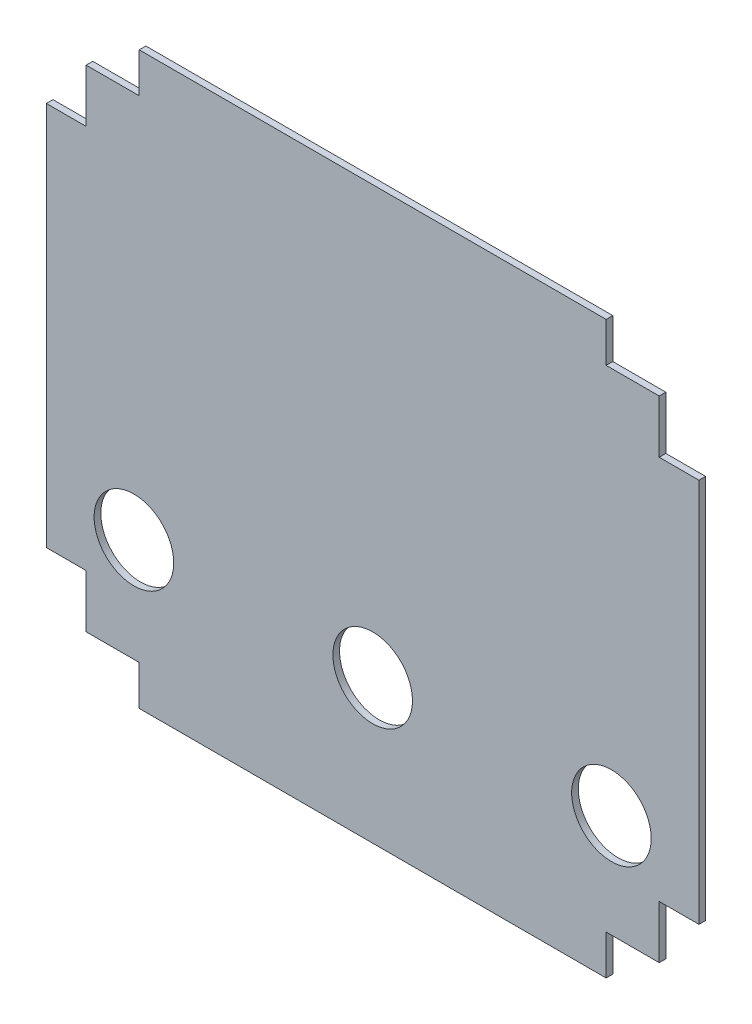
SolidWorks part; units mm, degrees
material "Acrílico (Impacto medio-alto)"
ref_plane "Alzado" through (0, 0, 0) normal (0, 0, 1) x (1, 0, 0)
ref_plane "Planta" through (0, 0, 0) normal (0, 1, 0) x (1, 0, 0)
ref_plane "Vista lateral" through (0, 0, 0) normal (1, 0, 0) x (0, 0, -1)
sketch "Croquis1" plane through (0, 0, 0) normal (0, 0, 1) x (1, 0, 0)
  line L0 (-246, 0) -> (246, 0)
  line L1 (0, 0) -> (0, 215) construction
  line L2 (-246, -145) -> (-246, 145)
  line L3 (-246, 145) -> (-216, 145)
  line L4 (-216, 145) -> (-216, 185)
  line L5 (-216, 185) -> (-176, 185)
  line L6 (-176, 185) -> (-176, 215)
  line L7 (-176, 215) -> (176, 215)
  line L8 (246, -145) -> (246, 145)
  line L9 (246, 145) -> (216, 145)
  line L10 (216, 145) -> (216, 185)
  line L11 (216, 185) -> (176, 185)
  line L12 (176, 185) -> (176, 215)
  line L13 (-246, -145) -> (-216, -145)
  line L14 (-216, -145) -> (-216, -185)
  line L15 (-216, -185) -> (-176, -185)
  line L16 (-176, -185) -> (-176, -215)
  line L17 (-176, -215) -> (176, -215)
  line L18 (176, -185) -> (176, -215)
  line L19 (216, -185) -> (176, -185)
  line L20 (216, -145) -> (216, -185)
  line L21 (246, -145) -> (216, -145)
  point P4 (0, 0)
  dimension "D1" = 492
  dimension "D2" = 145
  dimension "D3" = 216
  dimension "D4" = 176
  dimension "D5" = 30
  dimension "D6" = 40
extrude "Saliente-Extruir1" add sketch "Croquis1" along normal blind 5 contours L1 L0 L8 L9 L10 L11 L12 L7 | L0 L1 L7 L6 L5 L4 L3 L2 | L21 L8 L0 L2 L13 L14 L15 L16 L17 L18 L19 L20 region at (-116.66, 102.1915, 0) region at (0, -102.1915, 0) region at (116.66, 102.1915, 0)
sketch "Croquis2" plane through (0, 0, 5) normal (0, 0, 1) x (1, 0, 0)
  line L0 (-246, -145) -> (-246, 145) construction
  line L1 (-176, -215) -> (176, -215) construction
  circle A0 centre (-180, -107) radius 30
  circle A1 centre (0, -107) radius 30
  circle A2 centre (180, -107) radius 30
  dimension "D1" = 60
  dimension "D2" = 66
  dimension "D3" = 108
  dimension "D4" = 180
  dimension "D5" = 180
extrude "Cortar-Extruir1" cut sketch "Croquis2" against normal blind 10
